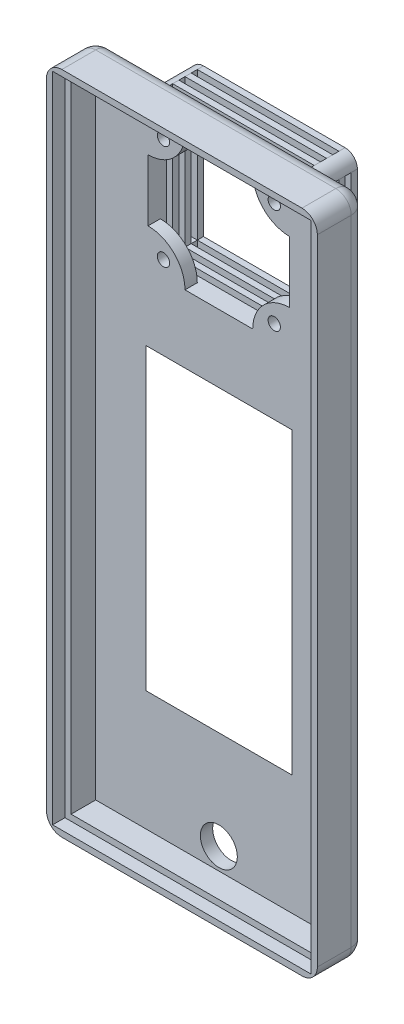
SolidWorks part; units mm, degrees
ref_plane "Přední rovina" through (0, 0, 0) normal (0, 0, 1) x (1, 0, 0)
ref_plane "Horní rovina" through (0, 0, 0) normal (0, 1, 0) x (1, 0, 0)
ref_plane "Pravá rovina" through (0, 0, 0) normal (1, 0, 0) x (0, 0, -1)
sketch "Skica1" plane through (0, 0, 0) normal (0, 0, 1) x (1, 0, 0)
  line L0 (-10.15, 2) -> (-10.15, 25)
  line L1 (0, -13) -> (0, -61.55)
  line L2 (-10.15, 25) -> (33.85, 25)
  line L3 (0, -61.55) -> (23.7, -61.55)
  line L4 (33.85, 25) -> (33.85, 2)
  line L5 (0.35, 20) -> (0.35, -2)
  line L7 (-10.15, -61.55) -> (-10.15, -83)
  line L8 (-10.15, -83) -> (33.85, -83)
  line L9 (33.85, -83) -> (33.85, 2)
  line L11 (-10.15, 2) -> (-10.15, -61.55)
  line L12 (23.7, -61.55) -> (23.7, -13)
  line L13 (23.7, -13) -> (0, -13)
  line L16 (0.35, 20) -> (23.35, 20)
  line L17 (23.35, 20) -> (23.35, -2)
  line L18 (23.35, -2) -> (0.35, -2)
  point P5 (11.85, 25)
  dimension "D2" = 48.55
  dimension "D3" = 23
  dimension "D4" = 23.7
  dimension "D5" = 63.55
  dimension "D6" = 5
  dimension "D8" = 21.45
  dimension "D9" = 44
  dimension "D10" = 85
  dimension "D11" = 22
extrude "Přidat vysunutím1" add sketch "Skica1" along normal blind 2
sketch "Skica3" plane through (0, 0, 2) normal (0, 0, 1) x (1, 0, 0)
  circle A0 centre (11.85, -77.5) radius 3
  dimension "D2" = 6
extrude "Odebrat vysunutím1" cut sketch "Skica3" against normal blind 4
chamfer "Zkosení1" distance 2 angle 60 4 edges at (0, -37.275, 0) (11.85, -61.55, 0) (23.7, -37.275, 0) (11.85, -13, 0) first distance on face at (0, -37.275, 1) first distance on face at (11.85, -61.55, 1) first distance on face at (23.7, -37.275, 1) first distance on face at (11.85, -13, 1)
sketch "Skica5" plane through (0, 0, 2) normal (0, 0, 1) x (1, 0, 0)
  line L1 (-10.15, 25) -> (33.85, 25)
  line L2 (-10.15, 25) -> (-10.15, -83)
  line L3 (-10.15, -83) -> (33.85, -83)
  line L4 (33.85, 25) -> (33.85, -83)
  line L5 (31.85, -81) -> (-8.15, -81)
  line L6 (31.85, -81) -> (31.85, 23)
  line L7 (31.85, 23) -> (-8.15, 23)
  line L8 (-8.15, -81) -> (-8.15, 23)
  dimension "D1" = 2
  dimension "D2" = 2
  dimension "D3" = 2
  dimension "D4" = 2
extrude "Přidat vysunutím3" add sketch "Skica5" along normal blind 6
fillet "Zaoblit2" radius 2.5 8 edges at (-10.15, -83, 4) (-10.15, 25, 4) (33.85, 25, 4) (33.85, -83, 4) (-10.15, -29, 0) (11.85, -83, 0) (33.85, -29, 0) (11.85, 25, 0)
sketch "Skica6" plane through (0, 0, 0) normal (0, 0, -1) x (-1, 0, 0)
  line L1 (-23.35, 20) -> (-0.35, 20)
  line L2 (-23.35, 20) -> (-23.35, -2)
  line L3 (-23.35, -2) -> (-0.35, -2)
  line L4 (-0.35, 20) -> (-0.35, -2)
  line L5 (1.65, -4) -> (-25.35, -4)
  line L6 (1.65, -4) -> (1.65, 22)
  line L7 (1.65, 22) -> (-25.35, 22)
  line L8 (-25.35, -4) -> (-25.35, 22)
  dimension "D1" = 2
  dimension "D2" = 2
  dimension "D3" = 2
  dimension "D4" = 2
extrude "Přidat vysunutím4" add sketch "Skica6" along normal blind 7
sketch "Skica7" plane through (0, 0, 0) normal (0, 0, -1) x (-1, 0, 0)
  line L0 (-23.35, -2) -> (-23.35, 4)
  line L1 (-23.35, 20) -> (-23.35, -2) construction
  line L2 (-0.35, 20) -> (-6.35, 20)
  line L3 (-0.35, 20) -> (-23.35, 20) construction
  line L16 (-0.35, 20) -> (-0.35, 14)
  line L17 (-0.35, -2) -> (-0.35, 20) construction
  line L18 (-0.35, -2) -> (-0.35, 4)
  line L19 (-0.35, -2) -> (-6.35, -2)
  line L20 (-23.35, -2) -> (-0.35, -2) construction
  line L21 (-23.35, -2) -> (-17.35, -2)
  line L22 (-23.35, 20) -> (-23.35, 14)
  line L23 (-23.35, 20) -> (-17.35, 20)
  circle A0 centre (-20.85, 17.5) radius 1
  circle A1 centre (-2.85, 17.5) radius 1
  circle A2 centre (-20.85, 0.5) radius 1
  circle A3 centre (-2.85, 0.5) radius 1
  arc A4 (-23.35, 14) -> (-17.35, 20) centre (-23.35, 20) ccw
  arc A5 (-6.35, 20) -> (-0.35, 14) centre (-0.35, 20) ccw
  arc A6 (-0.35, 4) -> (-6.35, -2) centre (-0.35, -2) ccw
  arc A7 (-17.35, -2) -> (-23.35, 4) centre (-23.35, -2) ccw
  dimension "D6" = 2
  dimension "D7" = 1
  dimension "D8" = 2.5
  dimension "D9" = 1
  dimension "D10" = 1
  dimension "D11" = 2.5
  dimension "D12" = 2.5
  dimension "D13" = 19.5
  dimension "D14" = 19.5
  dimension "D1" = 6
  dimension "D2" = 6
  dimension "D3" = 6
  dimension "D4" = 6
  dimension "D5" = 6
extrude "Přidat vysunutím5" add sketch "Skica7" against normal blind 2
sketch "Skica8" plane through (0, -4, 0) normal (0, -1, 0) x (1, 0, 0)
  line L0 (-1.65, -7) -> (-1.65, 0) construction
  line L1 (0.35, -6) -> (23.35, -6)
  line L2 (0.35, -6) -> (0.35, -5)
  line L3 (0.35, -5) -> (23.35, -5)
  line L4 (23.35, -6) -> (23.35, -5)
  line L5 (25.35, -7) -> (25.35, 0) construction
  line L6 (25.35, -7) -> (-1.65, -7) construction
  line L7 (0.35, -4) -> (23.35, -4)
  line L8 (0.35, -4) -> (0.35, -3)
  line L9 (0.35, -3) -> (23.35, -3)
  line L10 (23.35, -4) -> (23.35, -3)
  line L12 (0.35, -2) -> (23.35, -2)
  line L13 (0.35, -2) -> (0.35, -1)
  line L14 (0.35, -1) -> (23.35, -1)
  line L15 (23.35, -2) -> (23.35, -1)
  dimension "D1" = 1
  dimension "D2" = 1
  dimension "D3" = 2
  dimension "D4" = 2
  dimension "D5" = 1
  dimension "D6" = 1
  dimension "D7" = 1
  dimension "D8" = 23
  dimension "D9" = 1
extrude "Odebrat vysunutím3" cut sketch "Skica8" against normal blind 30
sketch "Skica9" plane through (-1.65, 0, 0) normal (-1, 0, 0) x (0, 0, 1)
  line L0 (-7, 22) -> (0, 22) construction
  line L1 (-6, 20) -> (-5, 20)
  line L2 (-6, 20) -> (-6, -2)
  line L3 (-6, -2) -> (-5, -2)
  line L4 (-5, 20) -> (-5, -2)
  line L5 (-7, -4) -> (0, -4) construction
  line L6 (-7, -4) -> (-7, 22) construction
  line L8 (-4, 20) -> (-3, 20)
  line L9 (-4, 20) -> (-4, -2)
  line L10 (-4, -2) -> (-3, -2)
  line L11 (-3, 20) -> (-3, -2)
  line L12 (-2, 20) -> (-1, 20)
  line L13 (-2, 20) -> (-2, -2)
  line L14 (-2, -2) -> (-1, -2)
  line L15 (-1, 20) -> (-1, -2)
  dimension "D1" = 2
  dimension "D2" = 2
  dimension "D3" = 1
  dimension "D4" = 1
  dimension "D5" = 22
  dimension "D6" = 1
  dimension "D7" = 1
  dimension "D8" = 1
  dimension "D9" = 1
extrude "Odebrat vysunutím4" cut sketch "Skica9" against normal blind 30
fillet "Zaoblit3" radius 2 4 edges at (25.35, -4, -3.5) (25.35, 22, -3.5) (-1.65, -4, -3.5) (-1.65, 22, -3.5)
sketch "Skica10" plane through (0, 0, 8) normal (0, 0, 1) x (1, 0, 0)
  line L0 (33.85, -80.5) -> (33.85, 22.5) construction
  line L1 (-9.15, 24) -> (32.85, 24)
  line L2 (-9.15, 24) -> (-9.15, -82)
  line L3 (-9.15, -82) -> (32.85, -82)
  line L4 (32.85, 24) -> (32.85, -82)
  line L5 (-10.15, 22.5) -> (-10.15, -80.5) construction
  line L6 (-7.65, -83) -> (31.35, -83) construction
  line L7 (31.35, 25) -> (-7.65, 25) construction
  line L9 (-8.15, 23) -> (31.85, 23)
  line L10 (-8.15, 23) -> (-8.15, -81)
  line L11 (-8.15, -81) -> (31.85, -81)
  line L12 (31.85, 23) -> (31.85, -81)
  dimension "D1" = 1
  dimension "D2" = 1
  dimension "D3" = 1
  dimension "D4" = 1
extrude "Odebrat vysunutím5" cut sketch "Skica10" against normal blind 2
ref_plane "Rovina1" through (-10.15, 22.5, 8) normal (0, -1, 0) x (-1, 0, 0)
